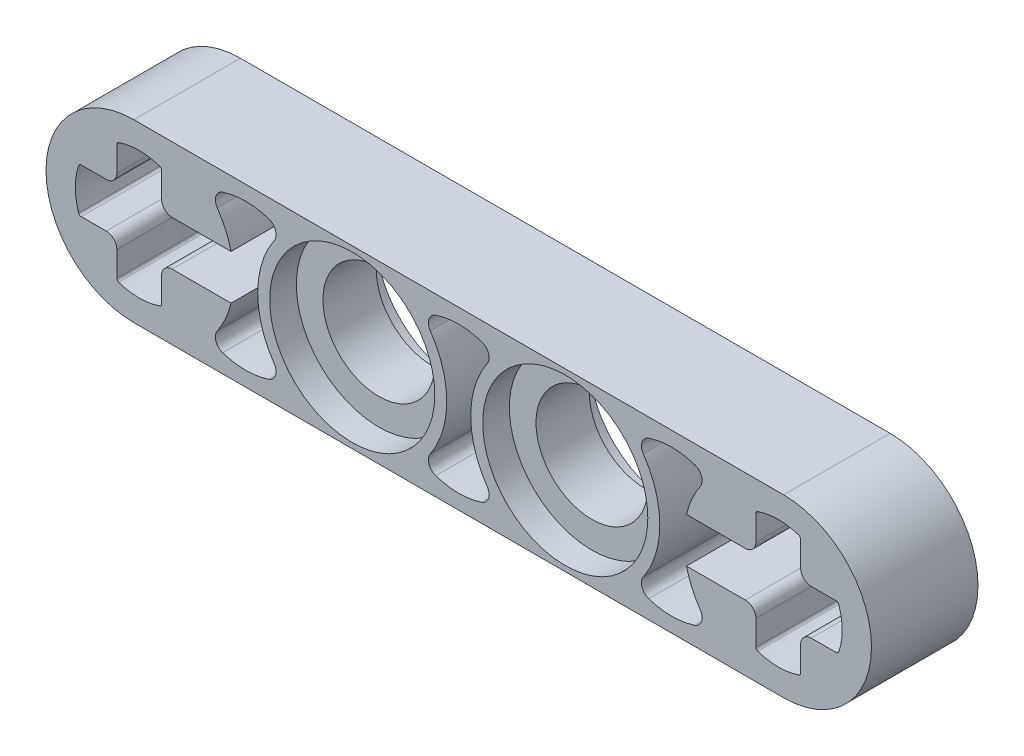
SolidWorks part; units mm, degrees
ref_plane "Front Plane" through (0, 0, 0) normal (0, 0, 1) x (1, 0, 0)
ref_plane "Top Plane" through (0, 0, 0) normal (0, 1, 0) x (1, 0, 0)
ref_plane "Right Plane" through (0, 0, 0) normal (1, 0, 0) x (0, 0, -1)
sketch "Sketch1" plane through (0, 0, 0) normal (0, 0, 1) x (1, 0, 0)
  line L14 (-13.24, 0.84) -> (-14.1777, 0.84)
  line L15 (-12.84, -2.1777) -> (-12.84, -1.24)
  line L16 (-11.16, -2.1777) -> (-11.16, -1.24)
  line L17 (-9.8223, 0.84) -> (-10.76, 0.84)
  line L18 (-9.8223, -0.84) -> (-10.76, -0.84)
  line L19 (-12.84, 1.24) -> (-12.84, 2.1777)
  line L20 (-11.16, 1.24) -> (-11.16, 2.1777)
  line L21 (-13.24, -0.84) -> (-14.1777, -0.84)
  line L22 (-9.7518, 0.84) -> (-8.5508, 0.84)
  line L23 (-9.7518, -0.84) -> (-8.5508, -0.84)
  line L24 (-9.8223, -0.84) -> (-9.7518, -0.84)
  line L25 (-9.8223, 0.84) -> (-9.7518, 0.84)
  line L26 (0, -55) -> (0, 55) construction
  line L27 (12.84, 1.24) -> (12.84, 2.1777)
  line L28 (11.16, 1.24) -> (11.16, 2.1777)
  line L29 (9.8223, 0.84) -> (10.76, 0.84)
  line L30 (9.8223, 0.84) -> (9.7518, 0.84)
  line L31 (9.7518, 0.84) -> (8.5508, 0.84)
  line L32 (9.7518, -0.84) -> (8.5508, -0.84)
  line L33 (9.8223, -0.84) -> (9.7518, -0.84)
  line L34 (9.8223, -0.84) -> (10.76, -0.84)
  line L35 (11.16, -2.1777) -> (11.16, -1.24)
  line L36 (12.84, -2.1777) -> (12.84, -1.24)
  line L37 (13.24, -0.84) -> (14.1777, -0.84)
  line L38 (13.24, 0.84) -> (14.1777, 0.84)
  line L44 (-12.2, 3.3) -> (12.2, 3.3)
  line L45 (-12.2, -3.3) -> (12.2, -3.3)
  circle A23 centre (-4, 0) radius 2.1
  arc A24 (-8.866, -2.6101) -> (-7.134, -2.6101) centre (-8, 0) ccw
  arc A25 (-6.9299, -2.0046) -> (-7.134, -2.6101) centre (-7.26, -2.2304) cw
  arc A26 (-6.9299, -2.0046) -> (-6.9299, 2.0046) centre (-4, 0) cw
  arc A27 (-6.9299, 2.0046) -> (-7.134, 2.6101) centre (-7.26, 2.2304) ccw
  arc A28 (-7.134, 2.6101) -> (-8.866, 2.6101) centre (-8, 0) ccw
  arc A29 (-9.0701, 2.0046) -> (-8.866, 2.6101) centre (-8.74, 2.2304) cw
  arc A30 (-9.0701, -2.0046) -> (-9.0701, 2.0046) centre (-12, 0) ccw
  arc A31 (-9.0701, -2.0046) -> (-8.866, -2.6101) centre (-8.74, -2.2304) ccw
  arc A32 (-11.2278, 2.2724) -> (-12.7722, 2.2724) centre (-12, 0) ccw
  arc A33 (-14.2724, 0.7722) -> (-14.2724, -0.7722) centre (-12, 0) ccw
  arc A34 (-12.7722, -2.2724) -> (-11.2278, -2.2724) centre (-12, 0) ccw
  arc A35 (-12.84, -1.24) -> (-13.24, -0.84) centre (-13.24, -1.24) ccw
  arc A36 (-11.16, -1.24) -> (-10.76, -0.84) centre (-10.76, -1.24) cw
  arc A37 (-10.76, 0.84) -> (-11.16, 1.24) centre (-10.76, 1.24) cw
  arc A38 (-13.24, 0.84) -> (-12.84, 1.24) centre (-13.24, 1.24) ccw
  arc A39 (-14.1777, 0.84) -> (-14.2724, 0.7722) centre (-14.1777, 0.74) ccw
  arc A40 (-14.1777, -0.84) -> (-14.2724, -0.7722) centre (-14.1777, -0.74) cw
  arc A41 (-12.7722, -2.2724) -> (-12.84, -2.1777) centre (-12.74, -2.1777) cw
  arc A42 (-11.2278, -2.2724) -> (-11.16, -2.1777) centre (-11.26, -2.1777) ccw
  arc A43 (-11.2278, 2.2724) -> (-11.16, 2.1777) centre (-11.26, 2.1777) cw
  arc A44 (-12.84, 2.1777) -> (-12.7722, 2.2724) centre (-12.74, 2.1777) cw
  arc A45 (-8.5508, -0.84) -> (-8.5508, 0.84) centre (-12, 0) ccw
  arc A46 (13.24, 0.84) -> (12.84, 1.24) centre (13.24, 1.24) cw
  arc A47 (12.84, 2.1777) -> (12.7722, 2.2724) centre (12.74, 2.1777) ccw
  arc A48 (11.2278, 2.2724) -> (12.7722, 2.2724) centre (12, 0) cw
  arc A49 (11.2278, 2.2724) -> (11.16, 2.1777) centre (11.26, 2.1777) ccw
  arc A50 (10.76, 0.84) -> (11.16, 1.24) centre (10.76, 1.24) ccw
  arc A51 (8.5508, -0.84) -> (8.5508, 0.84) centre (12, 0) cw
  arc A52 (11.16, -1.24) -> (10.76, -0.84) centre (10.76, -1.24) ccw
  arc A53 (11.2278, -2.2724) -> (11.16, -2.1777) centre (11.26, -2.1777) cw
  arc A54 (12.7722, -2.2724) -> (11.2278, -2.2724) centre (12, 0) cw
  arc A55 (12.7722, -2.2724) -> (12.84, -2.1777) centre (12.74, -2.1777) ccw
  arc A56 (12.84, -1.24) -> (13.24, -0.84) centre (13.24, -1.24) cw
  arc A57 (14.1777, -0.84) -> (14.2724, -0.7722) centre (14.1777, -0.74) ccw
  arc A58 (14.2724, 0.7722) -> (14.2724, -0.7722) centre (12, 0) cw
  arc A59 (14.1777, 0.84) -> (14.2724, 0.7722) centre (14.1777, 0.74) cw
  arc A60 (9.0701, -2.0046) -> (8.866, -2.6101) centre (8.74, -2.2304) cw
  arc A61 (9.0701, -2.0046) -> (9.0701, 2.0046) centre (12, 0) cw
  arc A62 (9.0701, 2.0046) -> (8.866, 2.6101) centre (8.74, 2.2304) ccw
  arc A63 (7.134, 2.6101) -> (8.866, 2.6101) centre (8, 0) cw
  arc A64 (6.9299, 2.0046) -> (7.134, 2.6101) centre (7.26, 2.2304) cw
  arc A65 (6.9299, -2.0046) -> (6.9299, 2.0046) centre (4, 0) ccw
  arc A66 (6.9299, -2.0046) -> (7.134, -2.6101) centre (7.26, -2.2304) ccw
  arc A67 (8.866, -2.6101) -> (7.134, -2.6101) centre (8, 0) cw
  circle A68 centre (4, 0) radius 2.1
  arc A73 (-12.2, 3.3) -> (-12.2, -3.3) centre (-12.2, 0) ccw
  arc A74 (12.2, 3.3) -> (12.2, -3.3) centre (12.2, 0) cw
  arc A75 (-0.866, -2.6101) -> (0.866, -2.6101) centre (0, 0) ccw
  arc A76 (1.0701, -2.0046) -> (0.866, -2.6101) centre (0.74, -2.2304) cw
  arc A77 (1.0701, -2.0046) -> (1.0701, 2.0046) centre (4, 0) cw
  arc A78 (1.0701, 2.0046) -> (0.866, 2.6101) centre (0.74, 2.2304) ccw
  arc A79 (0.866, 2.6101) -> (-0.866, 2.6101) centre (0, 0) ccw
  arc A80 (-1.0701, 2.0046) -> (-0.866, 2.6101) centre (-0.74, 2.2304) cw
  arc A81 (-1.0701, -2.0046) -> (-1.0701, 2.0046) centre (-4, 0) ccw
  arc A82 (-1.0701, -2.0046) -> (-0.866, -2.6101) centre (-0.74, -2.2304) ccw
  point P119 (0, 3.3)
  point P122 (0, -3.3)
  dimension "D2" = 4.2
  dimension "D3" = 4
extrude "Boss-Extrude1" add sketch "Sketch1" along normal mid plane 4 contours A74 L44 A73 L45 A82 A81 A80 A79 A78 A77 A76 A75 A60 A67 A66 A65 A64 A63 A62 A61 L31 L30 L29 A50 L28 A49 A48 A47 L27 A46 L38 A59 A58 A57 L37 A56 L36 A55 A54 A53 L35 A52 L34 L33 L32 L19 A44 region at (0, 2.9831, 0)
sketch "Sketch2" plane through (0, 0, 2) normal (0, 0, 1) x (1, 0, 0)
  circle A0 centre (-4, 0) radius 3.1
  circle A1 centre (4, 0) radius 3.1
  dimension "D1" = 6.2
  dimension "D2" = 6.2
extrude "Cut-Extrude1" cut sketch "Sketch2" against normal blind 1
mirror "Mirror1" about plane through (0, 0, 0) normal (0, 0, 1) of "Cut-Extrude1"
